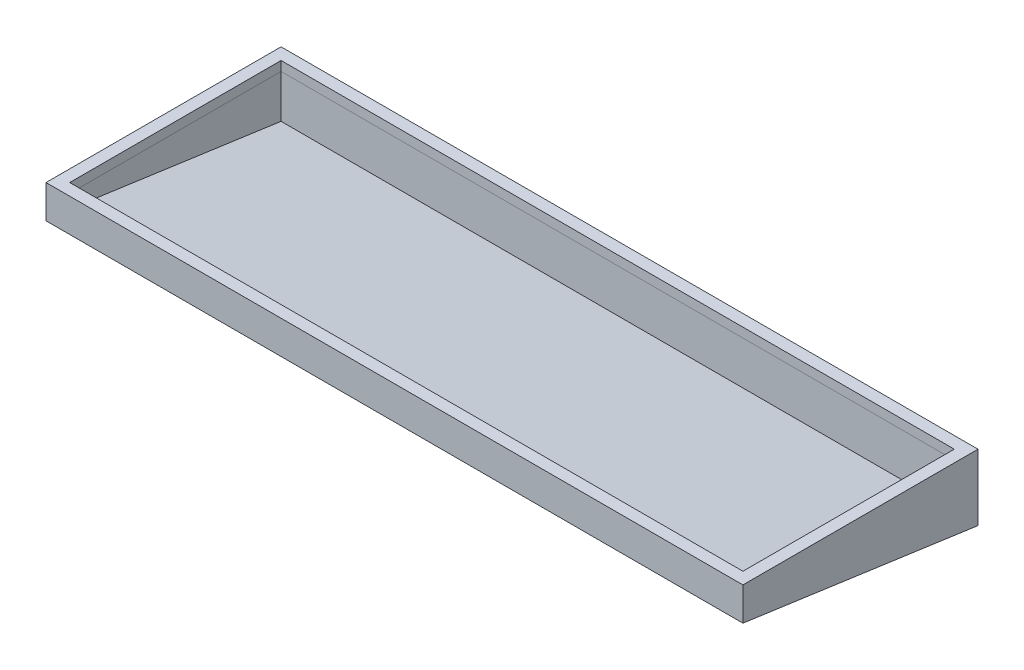
SolidWorks part; units mm, degrees
ref_plane "Front Plane" through (0, 0, 0) normal (0, 0, 1) x (1, 0, 0)
ref_plane "Top Plane" through (0, 0, 0) normal (0, 1, 0) x (1, 0, 0)
ref_plane "Right Plane" through (0, 0, 0) normal (1, 0, 0) x (0, 0, -1)
sketch "Sketch1" plane through (0, 0, 0) normal (0, 1, 0) x (1, 0, 0)
  line L1 (0, 0) -> (361, 0)
  line L2 (0, 0) -> (0, 113.35)
  line L3 (0, 113.35) -> (361, 113.35)
  line L4 (361, 0) -> (361, 113.35)
  line L5 (-6.35, -6.35) -> (367.35, -6.35)
  line L6 (-6.35, -6.35) -> (-6.35, 119.7)
  line L7 (-6.35, 119.7) -> (367.35, 119.7)
  line L8 (367.35, -6.35) -> (367.35, 119.7)
  dimension "D1" = 361
  dimension "D2" = 113.35
  dimension "D3" = 6.35
  dimension "D4" = 6.35
  dimension "D5" = 6.35
  dimension "D6" = 6.35
extrude "Boss-Extrude1" add sketch "Sketch1" along normal blind 5.08
sketch3d "3DSketch2"
  line L2 (367.35, -12.7, 6.35) -> (367.35, -30.4152, -119.7)
  line L3 (367.35, -12.7, 6.35) -> (-6.35, -12.7, 6.35)
  line L4 (-6.35, 0, 6.35) -> (367.35, 0, 6.35) construction
  line L5 (367.35, -30.4152, -119.7) -> (-6.35, -30.4152, -119.7)
  line L6 (367.35, 0, -119.7) -> (-6.35, 0, -119.7) construction
  line L7 (-6.35, -30.4152, -119.7) -> (-6.35, -12.7, 6.35)
  line L8 (367.35, 0, 6.35) -> (367.35, 0, -119.7) construction
  point P11 (0, 0, 0)
  point P13 (0, 0, 0)
  point P14 (0, 0, 0)
  point P15 (0, 0, 0)
  point P17 (0, 0, 0)
  point P21 (0, 0, 0)
  dimension "D1" = 12.7
  dimension "D2" = 8
sketch3d "3DSketch3"
  line L0 (367.35, -12.7, 6.35) -> (367.35, -30.4152, -119.7) construction
  line L1 (367.35, -12.7, 6.35) -> (-6.35, -12.7, 6.35) construction
sketch "Sketch3" plane through (0, -13.3292, 1.8733) normal (0, -0.9903, 0.1392) x (-1, 0, 0)
  line L0 (6.35, -4.5207) -> (-367.35, -4.5207)
  line L1 (-367.35, -4.5207) -> (-367.35, 122.7681)
  line L2 (-367.35, 122.7681) -> (6.35, 122.7681)
  line L3 (6.35, 122.7681) -> (6.35, -4.5207)
  point P8 (-22.2387, 122.7681)
  point P9 (0, 0)
extrude "Boss-Extrude2" add sketch "Sketch3" along direction (0, -1, 0) on the side against the normal up to surface (30.4152 mm away) up to face at (180.5, 0, -56.675)
shell "Shell1" thickness 5.875 removed face at (180.5, 0, -56.675)
